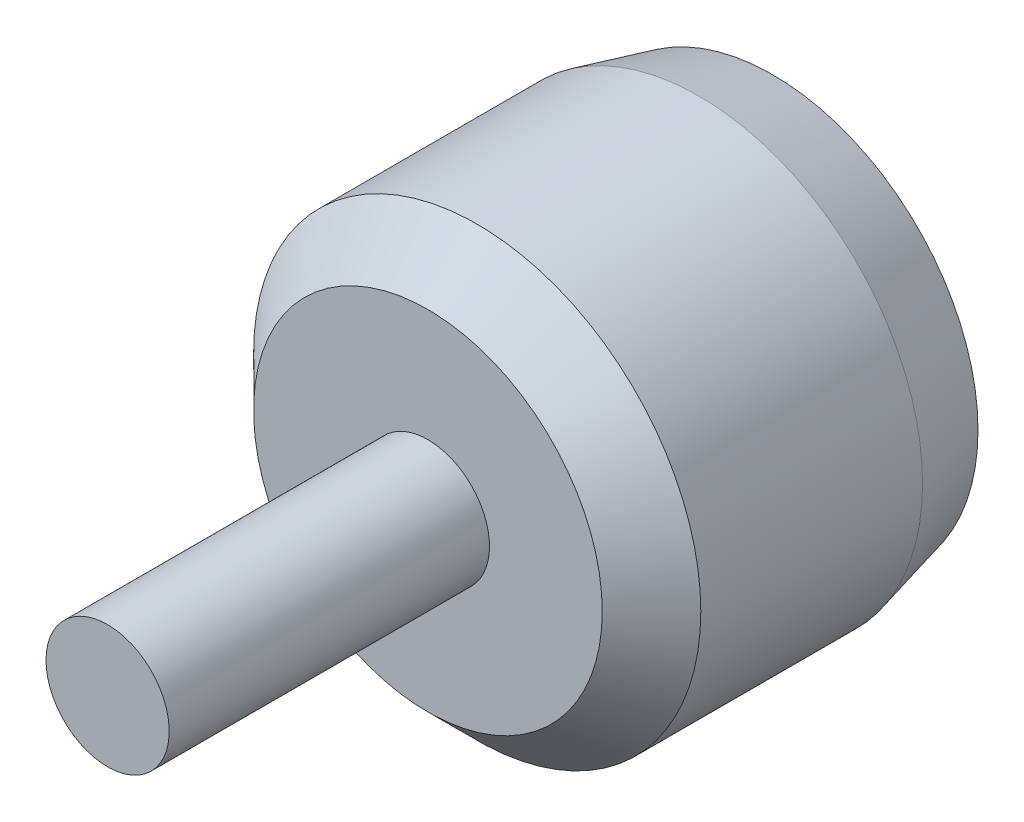
SolidWorks part; units mm, degrees
ref_plane "Front Plane" through (0, 0, 0) normal (0, 0, 1) x (1, 0, 0)
ref_plane "Top Plane" through (0, 0, 0) normal (0, 1, 0) x (1, 0, 0)
ref_plane "Right Plane" through (0, 0, 0) normal (1, 0, 0) x (0, 0, -1)
sketch "Sketch2" plane through (0, 0, 0) normal (0, 0, 1) x (1, 0, 0)
  circle A0 centre (0, 0) radius 9.075
  dimension "D1" = 18.15
extrude "Boss-Extrude1" add sketch "Sketch2" along normal blind 14
chamfer "Chamfer1" distance 2 angle 45 1 edges at (9.075, 0, 14)
chamfer "Chamfer2" distance 0.75 distance2 3 1 edges at (9.075, 0, 0) first distance on face at (9.075, 0, 0)
sketch "Sketch5" plane through (0, 0, 14) normal (0, 0, 1) x (1, 0, 0)
  circle A0 centre (0, 0) radius 2.5
  dimension "D1" = 5
extrude "Boss-Extrude2" add sketch "Sketch5" along normal blind 13
sketch "Sketch6" plane through (0, 0, 0) normal (0, 0, -1) x (-1, 0, 0)
  line L0 (-6, 0) -> (6, 0) construction
  line L1 (0, 6) -> (0, -6) construction
  circle A0 centre (0, 6) radius 1
  circle A1 centre (6, 0) radius 1
  circle A2 centre (0, -6) radius 1
  circle A3 centre (-6, 0) radius 1
  dimension "D2" = 2
  dimension "D1" = 12
sketch "Sketch7" plane through (0, 0, 0) normal (0, 0, -1) x (-1, 0, 0)
  circle A0 centre (0, 0) radius 8.35
  dimension "D1" = 16.7
extrude "Cut-Extrude1" cut sketch "Sketch6" against normal blind 2
